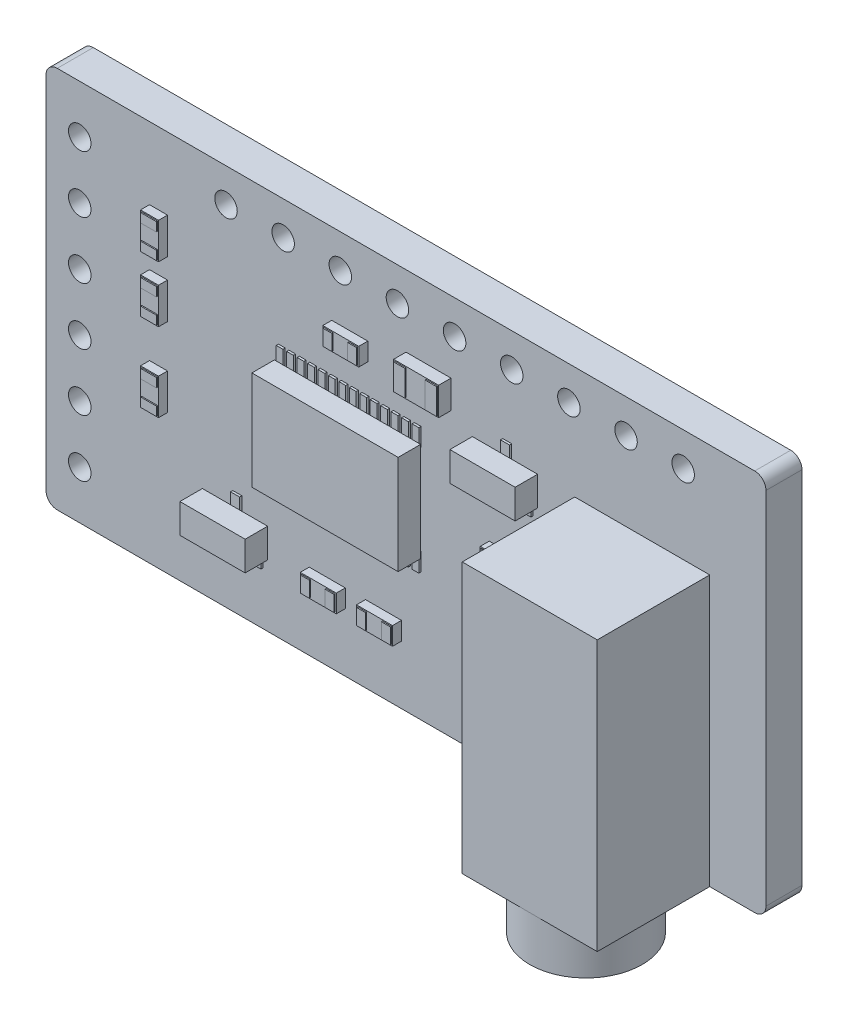
SolidWorks part; units mm, degrees
ref_plane "Front Plane" through (0, 0, 0) normal (0, 0, 1) x (1, 0, 0)
ref_plane "Top Plane" through (0, 0, 0) normal (0, 1, 0) x (1, 0, 0)
ref_plane "Right Plane" through (0, 0, 0) normal (1, 0, 0) x (0, 0, -1)
sketch "Sketch1" plane through (0, 0, 0) normal (0, 0, 1) x (1, 0, 0)
  line L0 (0.5, 0) -> (31.5, 0)
  line L1 (32, 0.5) -> (32, 16.5)
  line L2 (31.5, 17) -> (0.5, 17)
  line L3 (0, 16.5) -> (0, 0.5)
  arc A0 (31.5, 0) -> (32, 0.5) centre (31.5, 0.5) ccw
  arc A1 (32, 16.5) -> (31.5, 17) centre (31.5, 16.5) ccw
  arc A2 (0.5, 17) -> (0, 16.5) centre (0.5, 16.5) ccw
  arc A3 (0, 0.5) -> (0.5, 0) centre (0.5, 0.5) ccw
extrude "PCB" add sketch "Sketch1" along normal blind 1.6
ref_plane "Plane_z1_6" through (0, 0, 1.6) normal (0, 0, 1) x (1, 0, 0)
sketch "Sketch2" plane through (0, 0, 1.6) normal (0, 0, 1) x (1, 0, 0)
  line L1 (10.3321, 5.7) -> (10.6321, 5.7)
  line L2 (10.3321, 5.7) -> (10.3321, 6.5)
  line L3 (10.3321, 6.5) -> (10.6321, 6.5)
  line L4 (10.6321, 5.7) -> (10.6321, 6.5)
  line L6 (10.7964, 5.7) -> (11.0964, 5.7)
  line L7 (10.7964, 5.7) -> (10.7964, 6.5)
  line L8 (10.7964, 6.5) -> (11.0964, 6.5)
  line L9 (11.0964, 5.7) -> (11.0964, 6.5)
  line L11 (11.2607, 5.7) -> (11.5607, 5.7)
  line L12 (11.2607, 5.7) -> (11.2607, 6.5)
  line L13 (11.2607, 6.5) -> (11.5607, 6.5)
  line L14 (11.5607, 5.7) -> (11.5607, 6.5)
  line L16 (11.725, 5.7) -> (12.025, 5.7)
  line L17 (11.725, 5.7) -> (11.725, 6.5)
  line L18 (11.725, 6.5) -> (12.025, 6.5)
  line L19 (12.025, 5.7) -> (12.025, 6.5)
  line L21 (12.1893, 5.7) -> (12.4893, 5.7)
  line L22 (12.1893, 5.7) -> (12.1893, 6.5)
  line L23 (12.1893, 6.5) -> (12.4893, 6.5)
  line L24 (12.4893, 5.7) -> (12.4893, 6.5)
  line L26 (12.6536, 5.7) -> (12.9536, 5.7)
  line L27 (12.6536, 5.7) -> (12.6536, 6.5)
  line L28 (12.6536, 6.5) -> (12.9536, 6.5)
  line L29 (12.9536, 5.7) -> (12.9536, 6.5)
  line L31 (13.1179, 5.7) -> (13.4179, 5.7)
  line L32 (13.1179, 5.7) -> (13.1179, 6.5)
  line L33 (13.1179, 6.5) -> (13.4179, 6.5)
  line L34 (13.4179, 5.7) -> (13.4179, 6.5)
  line L36 (13.5821, 5.7) -> (13.8821, 5.7)
  line L37 (13.5821, 5.7) -> (13.5821, 6.5)
  line L38 (13.5821, 6.5) -> (13.8821, 6.5)
  line L39 (13.8821, 5.7) -> (13.8821, 6.5)
  line L41 (14.0464, 5.7) -> (14.3464, 5.7)
  line L42 (14.0464, 5.7) -> (14.0464, 6.5)
  line L43 (14.0464, 6.5) -> (14.3464, 6.5)
  line L44 (14.3464, 5.7) -> (14.3464, 6.5)
  line L46 (14.5107, 5.7) -> (14.8107, 5.7)
  line L47 (14.5107, 5.7) -> (14.5107, 6.5)
  line L48 (14.5107, 6.5) -> (14.8107, 6.5)
  line L49 (14.8107, 5.7) -> (14.8107, 6.5)
  line L51 (14.975, 5.7) -> (15.275, 5.7)
  line L52 (14.975, 5.7) -> (14.975, 6.5)
  line L53 (14.975, 6.5) -> (15.275, 6.5)
  line L54 (15.275, 5.7) -> (15.275, 6.5)
  line L56 (15.4393, 5.7) -> (15.7393, 5.7)
  line L57 (15.4393, 5.7) -> (15.4393, 6.5)
  line L58 (15.4393, 6.5) -> (15.7393, 6.5)
  line L59 (15.7393, 5.7) -> (15.7393, 6.5)
  line L61 (15.9036, 5.7) -> (16.2036, 5.7)
  line L62 (15.9036, 5.7) -> (15.9036, 6.5)
  line L63 (15.9036, 6.5) -> (16.2036, 6.5)
  line L64 (16.2036, 5.7) -> (16.2036, 6.5)
  line L66 (16.3679, 5.7) -> (16.6679, 5.7)
  line L67 (16.3679, 5.7) -> (16.3679, 6.5)
  line L68 (16.3679, 6.5) -> (16.6679, 6.5)
  line L69 (16.6679, 5.7) -> (16.6679, 6.5)
  line L71 (10.3321, 10.5) -> (10.6321, 10.5)
  line L72 (10.3321, 10.5) -> (10.3321, 11.3)
  line L73 (10.3321, 11.3) -> (10.6321, 11.3)
  line L74 (10.6321, 10.5) -> (10.6321, 11.3)
  line L76 (10.7964, 10.5) -> (11.0964, 10.5)
  line L77 (10.7964, 10.5) -> (10.7964, 11.3)
  line L78 (10.7964, 11.3) -> (11.0964, 11.3)
  line L79 (11.0964, 10.5) -> (11.0964, 11.3)
  line L81 (11.2607, 10.5) -> (11.5607, 10.5)
  line L82 (11.2607, 10.5) -> (11.2607, 11.3)
  line L83 (11.2607, 11.3) -> (11.5607, 11.3)
  line L84 (11.5607, 10.5) -> (11.5607, 11.3)
  line L86 (11.725, 10.5) -> (12.025, 10.5)
  line L87 (11.725, 10.5) -> (11.725, 11.3)
  line L88 (11.725, 11.3) -> (12.025, 11.3)
  line L89 (12.025, 10.5) -> (12.025, 11.3)
  line L91 (12.1893, 10.5) -> (12.4893, 10.5)
  line L92 (12.1893, 10.5) -> (12.1893, 11.3)
  line L93 (12.1893, 11.3) -> (12.4893, 11.3)
  line L94 (12.4893, 10.5) -> (12.4893, 11.3)
  line L96 (12.6536, 10.5) -> (12.9536, 10.5)
  line L97 (12.6536, 10.5) -> (12.6536, 11.3)
  line L98 (12.6536, 11.3) -> (12.9536, 11.3)
  line L99 (12.9536, 10.5) -> (12.9536, 11.3)
  line L101 (13.1179, 10.5) -> (13.4179, 10.5)
  line L102 (13.1179, 10.5) -> (13.1179, 11.3)
  line L103 (13.1179, 11.3) -> (13.4179, 11.3)
  line L104 (13.4179, 10.5) -> (13.4179, 11.3)
  line L106 (13.5821, 10.5) -> (13.8821, 10.5)
  line L107 (13.5821, 10.5) -> (13.5821, 11.3)
  line L108 (13.5821, 11.3) -> (13.8821, 11.3)
  line L109 (13.8821, 10.5) -> (13.8821, 11.3)
  line L111 (14.0464, 10.5) -> (14.3464, 10.5)
  line L112 (14.0464, 10.5) -> (14.0464, 11.3)
  line L113 (14.0464, 11.3) -> (14.3464, 11.3)
  line L114 (14.3464, 10.5) -> (14.3464, 11.3)
  line L116 (14.5107, 10.5) -> (14.8107, 10.5)
  line L117 (14.5107, 10.5) -> (14.5107, 11.3)
  line L118 (14.5107, 11.3) -> (14.8107, 11.3)
  line L119 (14.8107, 10.5) -> (14.8107, 11.3)
  line L121 (14.975, 10.5) -> (15.275, 10.5)
  line L122 (14.975, 10.5) -> (14.975, 11.3)
  line L123 (14.975, 11.3) -> (15.275, 11.3)
  line L124 (15.275, 10.5) -> (15.275, 11.3)
  line L126 (15.4393, 10.5) -> (15.7393, 10.5)
  line L127 (15.4393, 10.5) -> (15.4393, 11.3)
  line L128 (15.4393, 11.3) -> (15.7393, 11.3)
  line L129 (15.7393, 10.5) -> (15.7393, 11.3)
  line L131 (15.9036, 10.5) -> (16.2036, 10.5)
  line L132 (15.9036, 10.5) -> (15.9036, 11.3)
  line L133 (15.9036, 11.3) -> (16.2036, 11.3)
  line L134 (16.2036, 10.5) -> (16.2036, 11.3)
  line L136 (16.3679, 10.5) -> (16.6679, 10.5)
  line L137 (16.3679, 10.5) -> (16.3679, 11.3)
  line L138 (16.3679, 11.3) -> (16.6679, 11.3)
  line L139 (16.6679, 10.5) -> (16.6679, 11.3)
  line L141 (19.35, 10.35) -> (19.75, 10.35)
  line L142 (19.35, 10.35) -> (19.35, 11.05)
  line L143 (19.35, 11.05) -> (19.75, 11.05)
  line L144 (19.75, 10.35) -> (19.75, 11.05)
  line L146 (21.25, 10.35) -> (21.65, 10.35)
  line L147 (21.25, 10.35) -> (21.25, 11.05)
  line L148 (21.25, 11.05) -> (21.65, 11.05)
  line L149 (21.65, 10.35) -> (21.65, 11.05)
  line L151 (20.3, 11.95) -> (20.7, 11.95)
  line L152 (20.3, 11.95) -> (20.3, 12.65)
  line L153 (20.3, 12.65) -> (20.7, 12.65)
  line L154 (20.7, 11.95) -> (20.7, 12.65)
  line L156 (7.35, 2.35) -> (7.75, 2.35)
  line L157 (7.35, 2.35) -> (7.35, 3.05)
  line L158 (7.35, 3.05) -> (7.75, 3.05)
  line L159 (7.75, 2.35) -> (7.75, 3.05)
  line L161 (9.25, 2.35) -> (9.65, 2.35)
  line L162 (9.25, 2.35) -> (9.25, 3.05)
  line L163 (9.25, 3.05) -> (9.65, 3.05)
  line L164 (9.65, 2.35) -> (9.65, 3.05)
  line L166 (8.3, 3.95) -> (8.7, 3.95)
  line L167 (8.3, 3.95) -> (8.3, 4.65)
  line L168 (8.3, 4.65) -> (8.7, 4.65)
  line L169 (8.7, 3.95) -> (8.7, 4.65)
extrude "SMD_add00" add sketch "Sketch2" along normal blind 0.1
sketch "Sketch3" plane through (0, 0, 1.6) normal (0, 0, 1) x (1, 0, 0)
  line L1 (4.6, 6.2) -> (5.4, 6.2)
  line L2 (4.6, 6.2) -> (4.6, 7.8)
  line L3 (4.6, 7.8) -> (5.4, 7.8)
  line L4 (5.4, 6.2) -> (5.4, 7.8)
  line L6 (4.6, 9.7) -> (5.4, 9.7)
  line L7 (4.6, 9.7) -> (4.6, 11.3)
  line L8 (4.6, 11.3) -> (5.4, 11.3)
  line L9 (5.4, 9.7) -> (5.4, 11.3)
  line L11 (4.6, 12.2) -> (5.4, 12.2)
  line L12 (4.6, 12.2) -> (4.6, 13.8)
  line L13 (4.6, 13.8) -> (5.4, 13.8)
  line L14 (5.4, 12.2) -> (5.4, 13.8)
  line L16 (19.7, 7.6) -> (21.3, 7.6)
  line L17 (19.7, 7.6) -> (19.7, 8.4)
  line L18 (19.7, 8.4) -> (21.3, 8.4)
  line L19 (21.3, 7.6) -> (21.3, 8.4)
  line L21 (19.7, 5.6) -> (21.3, 5.6)
  line L22 (19.7, 5.6) -> (19.7, 6.4)
  line L23 (19.7, 6.4) -> (21.3, 6.4)
  line L24 (21.3, 5.6) -> (21.3, 6.4)
  line L26 (19.7, 3.6) -> (21.3, 3.6)
  line L27 (19.7, 3.6) -> (19.7, 4.4)
  line L28 (19.7, 4.4) -> (21.3, 4.4)
  line L29 (21.3, 3.6) -> (21.3, 4.4)
  line L31 (14.2, 2.6) -> (15.8, 2.6)
  line L32 (14.2, 2.6) -> (14.2, 3.4)
  line L33 (14.2, 3.4) -> (15.8, 3.4)
  line L34 (15.8, 2.6) -> (15.8, 3.4)
  line L36 (11.7, 2.6) -> (13.3, 2.6)
  line L37 (11.7, 2.6) -> (11.7, 3.4)
  line L38 (11.7, 3.4) -> (13.3, 3.4)
  line L39 (13.3, 2.6) -> (13.3, 3.4)
  line L41 (12.7, 12.6) -> (14.3, 12.6)
  line L42 (12.7, 12.6) -> (12.7, 13.4)
  line L43 (12.7, 13.4) -> (14.3, 13.4)
  line L44 (14.3, 12.6) -> (14.3, 13.4)
extrude "SMD_add01" add sketch "Sketch3" along normal blind 0.4
sketch "Sketch4" plane through (0, 0, 1.6) normal (0, 0, 1) x (1, 0, 0)
  line L1 (16, 12.575) -> (18, 12.575)
  line L2 (16, 12.575) -> (16, 13.825)
  line L3 (16, 13.825) -> (18, 13.825)
  line L4 (18, 12.575) -> (18, 13.825)
extrude "SMD_add02" add sketch "Sketch4" along normal blind 0.55
ref_plane "Plane_z1_7" through (0, 0, 1.7) normal (0, 0, 1) x (1, 0, 0)
sketch "Sketch5" plane through (0, 0, 1.7) normal (0, 0, 1) x (1, 0, 0)
  line L1 (10.25, 6.3) -> (16.75, 6.3)
  line L2 (10.25, 6.3) -> (10.25, 10.7)
  line L3 (10.25, 10.7) -> (16.75, 10.7)
  line L4 (16.75, 6.3) -> (16.75, 10.7)
  line L6 (19.05, 10.85) -> (21.95, 10.85)
  line L7 (19.05, 10.85) -> (19.05, 12.15)
  line L8 (19.05, 12.15) -> (21.95, 12.15)
  line L9 (21.95, 10.85) -> (21.95, 12.15)
  line L11 (7.05, 2.85) -> (9.95, 2.85)
  line L12 (7.05, 2.85) -> (7.05, 4.15)
  line L13 (7.05, 4.15) -> (9.95, 4.15)
  line L14 (9.95, 2.85) -> (9.95, 4.15)
extrude "SMD_add03" add sketch "Sketch5" along normal blind 1
ref_plane "Plane_z2" through (0, 0, 2) normal (0, 0, 1) x (1, 0, 0)
sketch "Sketch6" plane through (0, 0, 2) normal (0, 0, 1) x (1, 0, 0)
  line L1 (4.65, 6.25) -> (5.35, 6.25)
  line L2 (4.65, 6.25) -> (4.65, 6.65)
  line L3 (4.65, 6.65) -> (5.35, 6.65)
  line L4 (5.35, 6.25) -> (5.35, 6.65)
  line L6 (4.65, 7.35) -> (5.35, 7.35)
  line L7 (4.65, 7.35) -> (4.65, 7.75)
  line L8 (4.65, 7.75) -> (5.35, 7.75)
  line L9 (5.35, 7.35) -> (5.35, 7.75)
  line L11 (4.65, 9.75) -> (5.35, 9.75)
  line L12 (4.65, 9.75) -> (4.65, 10.15)
  line L13 (4.65, 10.15) -> (5.35, 10.15)
  line L14 (5.35, 9.75) -> (5.35, 10.15)
  line L16 (4.65, 10.85) -> (5.35, 10.85)
  line L17 (4.65, 10.85) -> (4.65, 11.25)
  line L18 (4.65, 11.25) -> (5.35, 11.25)
  line L19 (5.35, 10.85) -> (5.35, 11.25)
  line L21 (4.65, 12.25) -> (5.35, 12.25)
  line L22 (4.65, 12.25) -> (4.65, 12.65)
  line L23 (4.65, 12.65) -> (5.35, 12.65)
  line L24 (5.35, 12.25) -> (5.35, 12.65)
  line L26 (4.65, 13.35) -> (5.35, 13.35)
  line L27 (4.65, 13.35) -> (4.65, 13.75)
  line L28 (4.65, 13.75) -> (5.35, 13.75)
  line L29 (5.35, 13.35) -> (5.35, 13.75)
  line L31 (19.75, 7.65) -> (20.15, 7.65)
  line L32 (19.75, 7.65) -> (19.75, 8.35)
  line L33 (19.75, 8.35) -> (20.15, 8.35)
  line L34 (20.15, 7.65) -> (20.15, 8.35)
  line L36 (20.85, 7.65) -> (21.25, 7.65)
  line L37 (20.85, 7.65) -> (20.85, 8.35)
  line L38 (20.85, 8.35) -> (21.25, 8.35)
  line L39 (21.25, 7.65) -> (21.25, 8.35)
  line L41 (19.75, 5.65) -> (20.15, 5.65)
  line L42 (19.75, 5.65) -> (19.75, 6.35)
  line L43 (19.75, 6.35) -> (20.15, 6.35)
  line L44 (20.15, 5.65) -> (20.15, 6.35)
  line L46 (20.85, 5.65) -> (21.25, 5.65)
  line L47 (20.85, 5.65) -> (20.85, 6.35)
  line L48 (20.85, 6.35) -> (21.25, 6.35)
  line L49 (21.25, 5.65) -> (21.25, 6.35)
  line L51 (19.75, 3.65) -> (20.15, 3.65)
  line L52 (19.75, 3.65) -> (19.75, 4.35)
  line L53 (19.75, 4.35) -> (20.15, 4.35)
  line L54 (20.15, 3.65) -> (20.15, 4.35)
  line L56 (20.85, 3.65) -> (21.25, 3.65)
  line L57 (20.85, 3.65) -> (20.85, 4.35)
  line L58 (20.85, 4.35) -> (21.25, 4.35)
  line L59 (21.25, 3.65) -> (21.25, 4.35)
  line L61 (14.25, 2.65) -> (14.65, 2.65)
  line L62 (14.25, 2.65) -> (14.25, 3.35)
  line L63 (14.25, 3.35) -> (14.65, 3.35)
  line L64 (14.65, 2.65) -> (14.65, 3.35)
  line L66 (15.35, 2.65) -> (15.75, 2.65)
  line L67 (15.35, 2.65) -> (15.35, 3.35)
  line L68 (15.35, 3.35) -> (15.75, 3.35)
  line L69 (15.75, 2.65) -> (15.75, 3.35)
  line L71 (11.75, 2.65) -> (12.15, 2.65)
  line L72 (11.75, 2.65) -> (11.75, 3.35)
  line L73 (11.75, 3.35) -> (12.15, 3.35)
  line L74 (12.15, 2.65) -> (12.15, 3.35)
  line L76 (12.85, 2.65) -> (13.25, 2.65)
  line L77 (12.85, 2.65) -> (12.85, 3.35)
  line L78 (12.85, 3.35) -> (13.25, 3.35)
  line L79 (13.25, 2.65) -> (13.25, 3.35)
  line L81 (12.75, 12.65) -> (13.15, 12.65)
  line L82 (12.75, 12.65) -> (12.75, 13.35)
  line L83 (12.75, 13.35) -> (13.15, 13.35)
  line L84 (13.15, 12.65) -> (13.15, 13.35)
  line L86 (13.85, 12.65) -> (14.25, 12.65)
  line L87 (13.85, 12.65) -> (13.85, 13.35)
  line L88 (13.85, 13.35) -> (14.25, 13.35)
  line L89 (14.25, 12.65) -> (14.25, 13.35)
extrude "SMD_add04" add sketch "Sketch6" along normal blind 0.05
ref_plane "Plane_z2_15" through (0, 0, 2.15) normal (0, 0, 1) x (1, 0, 0)
sketch "Sketch7" plane through (0, 0, 2.15) normal (0, 0, 1) x (1, 0, 0)
  line L1 (16.05, 12.625) -> (16.55, 12.625)
  line L2 (16.05, 12.625) -> (16.05, 13.775)
  line L3 (16.05, 13.775) -> (16.55, 13.775)
  line L4 (16.55, 12.625) -> (16.55, 13.775)
  line L6 (17.45, 12.625) -> (17.95, 12.625)
  line L7 (17.45, 12.625) -> (17.45, 13.775)
  line L8 (17.45, 13.775) -> (17.95, 13.775)
  line L9 (17.95, 12.625) -> (17.95, 13.775)
extrude "SMD_add05" add sketch "Sketch7" along normal blind 0.05
sketch "Sketch8" plane through (0, 0, 1.6) normal (0, 0, 1) x (1, 0, 0)
  line L1 (23.5, 0) -> (29.5, 0)
  line L2 (23.5, 0) -> (23.5, 12)
  line L3 (23.5, 12) -> (29.5, 12)
  line L4 (29.5, 0) -> (29.5, 12)
extrude "Body00" add sketch "Sketch8" along normal blind 5
sketch "Sketch9" plane through (0, 0, 0) normal (0, 1, 0) x (1, 0, 0)
  circle A0 centre (26.5, -4.1) radius 2.5
extrude "Side0_J1_jack_nose" add sketch "Sketch9" against normal blind 2
sketch "Sketch10" plane through (0, 0, 0) normal (0, 1, 0) x (1, 0, 0)
  circle A0 centre (26.5, -4.1) radius 1.75
extrude "SideBore0_J1_jack_nose" cut sketch "Sketch10" against normal blind 2
sketch "Sketch11" plane through (0, 0, 1.6) normal (0, 0, 1) x (1, 0, 0)
  circle A0 centre (1.5, 2.15) radius 0.5
  circle A1 centre (1.5, 4.69) radius 0.5
  circle A2 centre (1.5, 7.23) radius 0.5
  circle A3 centre (1.5, 9.77) radius 0.5
  circle A4 centre (1.5, 12.31) radius 0.5
  circle A5 centre (1.5, 14.85) radius 0.5
  circle A6 centre (8, 15.5) radius 0.5
  circle A7 centre (10.54, 15.5) radius 0.5
  circle A8 centre (13.08, 15.5) radius 0.5
  circle A9 centre (15.62, 15.5) radius 0.5
  circle A10 centre (18.16, 15.5) radius 0.5
  circle A11 centre (20.7, 15.5) radius 0.5
  circle A12 centre (23.24, 15.5) radius 0.5
  circle A13 centre (25.78, 15.5) radius 0.5
  circle A14 centre (28.32, 15.5) radius 0.5
extrude "Holes" cut sketch "Sketch11" against normal blind 1.6
equation "\"pcb_t\" = 1.6mm"
equation "\"D1@PCB\" = \"pcb_t\""
